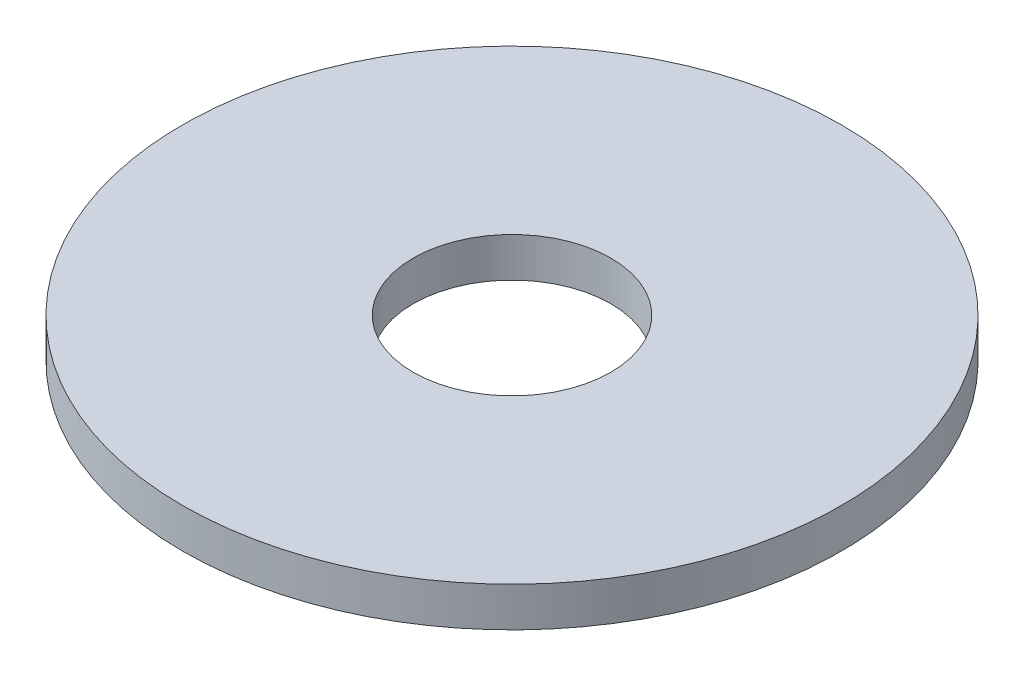
SolidWorks part; units mm, degrees
ref_plane "Front Plane" through (0, 0, 0) normal (0, 0, 1) x (1, 0, 0)
ref_plane "Top Plane" through (0, 0, 0) normal (0, 1, 0) x (1, 0, 0)
ref_plane "Right Plane" through (0, 0, 0) normal (1, 0, 0) x (0, 0, -1)
sketch "Sketch1" plane through (0, 0, 0) normal (0, 1, 0) x (1, 0, 0)
  circle A0 centre (0, 0) radius 75
  dimension "FLANGE_OD" = 150
extrude "Boss-Extrude1" add sketch "Sketch1" along normal blind 9
sketch "Sketch2" plane through (0, 0, 0) normal (0, 1, 0) x (1, 0, 0)
  circle A0 centre (0, 0) radius 22.5
  dimension "BORE_D" = 45
extrude "Cut-Extrude1" cut sketch "Sketch2" along normal through all
sketch "Sketch3" plane through (0, 9, 0) normal (0, 1, 0) x (1, 0, 0)
  circle A0 centre (0, 0) radius 17.999 construction
  circle A1 centre (-17.999, 0) radius 2.5927
  dimension "BOLT_D" = 5.1854
  dimension "BOLT_PCD" = 35.998
extrude "Cut-Extrude2" cut sketch "Sketch3" against normal blind 6.9858 rebuild error yes
pattern_circular "CirPattern1" count 4 over 360 rebuild error yes
